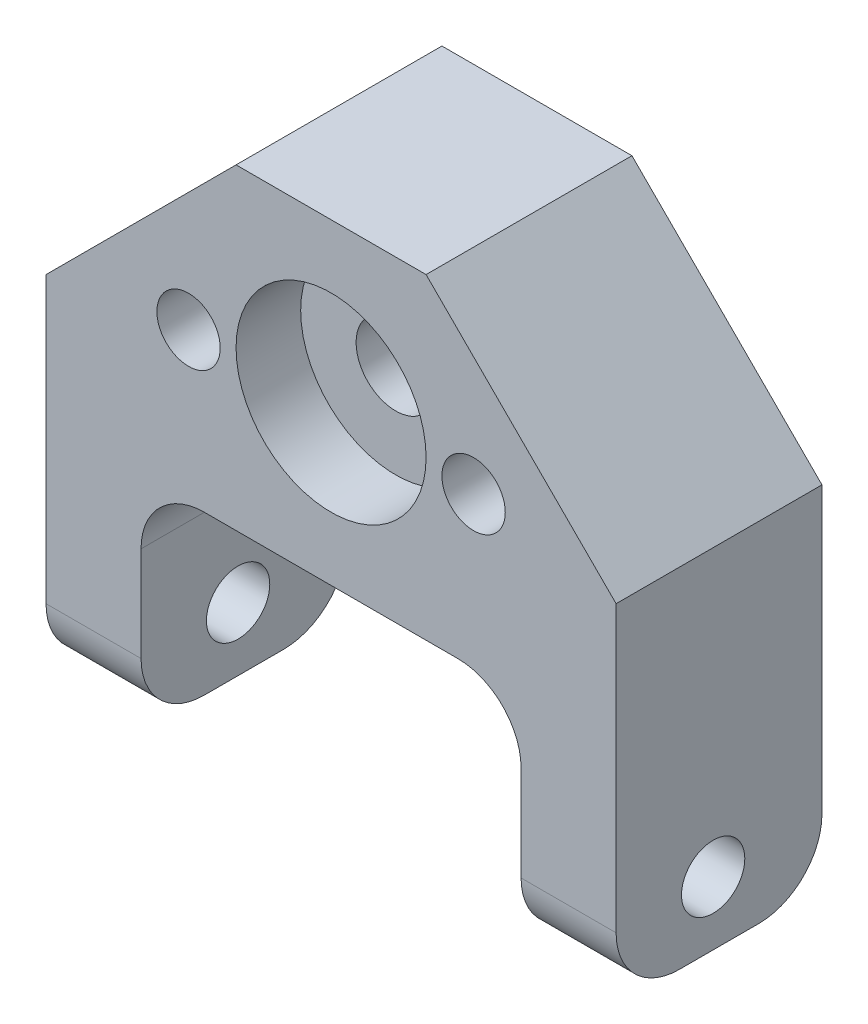
SolidWorks part; units mm, degrees
material "6063-O"
ref_plane "Front" through (0, 0, 0) normal (0, 0, 1) x (1, 0, 0)
ref_plane "Top" through (0, 0, 0) normal (0, 1, 0) x (1, 0, 0)
ref_plane "Right" through (0, 0, 0) normal (1, 0, 0) x (0, 0, -1)
sketch "Sketch1" plane through (0, 0, 0) normal (0, 0, 1) x (1, 0, 0)
  line L1 (28.575, -15.875) -> (-28.575, -15.875)
  line L2 (28.575, -15.875) -> (28.575, 15.875)
  line L3 (28.575, 15.875) -> (-28.575, 15.875)
  line L4 (-28.575, -15.875) -> (-28.575, 15.875)
  line L5 (28.575, -15.875) -> (-28.575, 15.875) construction
  line L6 (28.575, 15.875) -> (-28.575, -15.875) construction
  point P0 (0, 0)
  dimension "D1" = 31.75
  dimension "D2" = 57.15
extrude "Boss-Extrude1" add sketch "Sketch1" along normal blind 20.6375
sketch "Sketch2" plane through (0, 0, 0) normal (0, 0, -1) x (-1, 0, 0)
  circle A0 centre (0, 0) radius 11.1125
  dimension "D1" = 22.225
extrude "Cut-Extrude1" cut sketch "Sketch2" against normal blind 6.985
sketch "Sketch3" plane through (0, 0, 6.985) normal (0, 0, -1) x (-1, 0, 0)
  circle A0 centre (0, 0) radius 8.255
  dimension "D1" = 16.51
extrude "Cut-Extrude2" cut sketch "Sketch3" against normal blind 2.413
sketch "Sketch4" plane through (0, 0, 9.398) normal (0, 0, -1) x (-1, 0, 0)
  circle A0 centre (0, 0) radius 3.9688
  dimension "D1" = 7.9375
extrude "Cut-Extrude3" cut sketch "Sketch4" against normal through all
sketch "Sketch6" plane through (0, 0, 9.398) normal (0, 0, -1) x (-1, 0, 0)
  circle A0 centre (0, 0) radius 9.525
  dimension "D1" = 19.05
extrude "Cut-Extrude4" cut sketch "Sketch6" against normal through all from offset 4.7625 offset against normal yes
sketch "Sketch7" plane through (0, -15.875, 0) normal (0, -1, 0) x (1, 0, 0)
  line L0 (-28.575, 0) -> (28.575, 0) construction
  line L1 (-28.575, 20.6375) -> (-19.05, 20.6375)
  line L2 (-28.575, 20.6375) -> (-28.575, 0)
  line L3 (-28.575, 0) -> (-19.05, 0)
  line L4 (-19.05, 20.6375) -> (-19.05, 0)
  line L6 (28.575, 20.6375) -> (19.05, 20.6375)
  line L7 (28.575, 20.6375) -> (28.575, 0)
  line L8 (28.575, 0) -> (19.05, 0)
  line L9 (19.05, 20.6375) -> (19.05, 0)
  dimension "D1" = 9.525
extrude "Boss-Extrude2" add sketch "Sketch7" along normal blind 22.225
sketch "Sketch9" plane through (28.575, 0, 0) normal (1, 0, 0) x (0, 0, -1)
  line L0 (0, -38.1) -> (-20.6375, -38.1) construction
  circle A0 centre (-10.9095, -31.75) radius 3.175
  dimension "D2" = 6.35
  dimension "D1" = 6.35
extrude "Cut-Extrude5" cut sketch "Sketch9" against normal through all
fillet "Fillet1" radius 6.35 2 edges at (19.05, -15.875, 10.3187) (-19.05, -15.875, 10.3187)
hole_wizard "1/4 (0.2500) Dowel Hole1" positions "Sketch10" profile "Sketch11" hole size "1/4" standard "ANSI Inch"
sketch "Sketch10" plane through (0, 0, 20.6375) normal (0, 0, 1) x (1, 0, 0)
  line L0 (-28.575, 15.875) -> (-28.575, -38.1) construction
  line L1 (28.575, -38.1) -> (28.575, 15.875) construction
  line L2 (28.575, 15.875) -> (-28.575, 15.875) construction
  point P0 (-14.2875, -0.8255)
  point P2 (14.2875, -0.8052)
  dimension "D1" = 14.2875
  dimension "D2" = 14.2875
  dimension "D3" = 16.7005
  dimension "D4" = 16.6802
sketch "Sketch11" plane through (-14.2875, -0.8255, 20.6375) normal (1, 0, 0) x (0, -1, 0)
  line L0 (0, 0) -> (0, 11.5597)
  line L1 (0, 11.5597) -> (3.175, 9.652)
  line L2 (3.175, 9.652) -> (3.175, 0)
  line L5 (3.175, 0) -> (0, 0)
  line L10 (0, 11.5597) -> (-3.175, 9.652) construction
  line L11 (0, -6.35) -> (0, 107.95) construction
  dimension "Hole Dia." = 6.35
  dimension "Hole Depth" = 9.652
  dimension "Drill Angle" = 118
fillet "Fillet3" radius 6.35 4 edges at (23.8125, -38.1, 0) (23.8125, -38.1, 20.6375) (-23.8125, -38.1, 20.6375) (-23.8125, -38.1, 0)
chamfer "Chamfer1" distance 19.05 angle 45 2 edges at (28.575, 15.875, 10.3187) (-28.575, 15.875, 10.3187)
